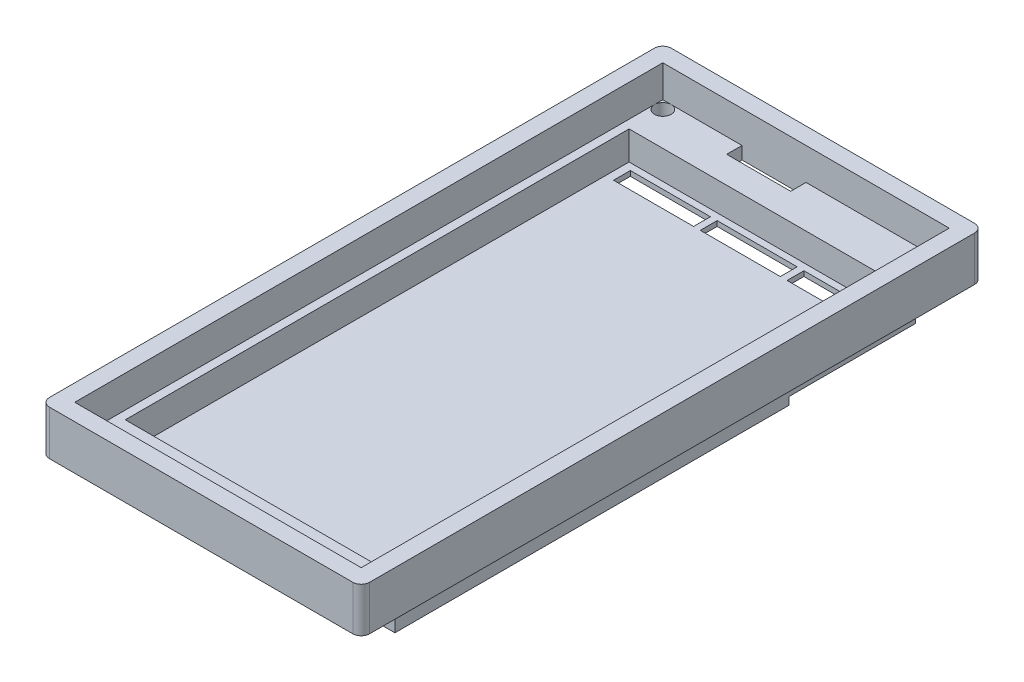
SolidWorks part; units mm, degrees
ref_plane "Front Plane" through (0, 0, 0) normal (0, 0, 1) x (1, 0, 0)
ref_plane "Top Plane" through (0, 0, 0) normal (0, 1, 0) x (1, 0, 0)
ref_plane "Right Plane" through (0, 0, 0) normal (1, 0, 0) x (0, 0, -1)
ref_axis "X-Axis" through (-88.99, 0, 0) along (1, 0, 0)
ref_axis "Y-Axis" through (0, 55, 0) along (0, -1, 0)
ref_axis "Z-Axis" through (0, 0, -88.99) along (0, 0, 1)
sketch "Sketch1" plane through (0, 0, 0) normal (0, 1, 0) x (1, 0, 0)
  line L1 (-19, -36.9) -> (19, -36.9)
  line L2 (-19, -36.9) -> (-19, 36.9)
  line L3 (-19, 36.9) -> (19, 36.9)
  line L4 (19, -36.9) -> (19, 36.9)
  line L5 (-19, -36.9) -> (19, 36.9) construction
  line L6 (-19, 36.9) -> (19, -36.9) construction
  point P0 (0, 0)
  dimension "D1" = 73.8
  dimension "D2" = 38
extrude "Boss-Extrude1" add sketch "Sketch1" along normal blind 1.5
sketch "Sketch2" plane through (0, 1.5, 0) normal (0, 1, 0) x (1, 0, 0)
  line L8 (17, -34.9) -> (17, 34.9)
  line L9 (17, 34.9) -> (-17, 34.9)
  line L10 (-17, 34.9) -> (-17, -34.9)
  line L11 (-17, -34.9) -> (17, -34.9)
  line L12 (17, -34.9) -> (17, 34.9)
  line L13 (17, 34.9) -> (-17, 34.9)
  line L14 (-17, 34.9) -> (-17, -34.9)
  line L15 (-17, -34.9) -> (17, -34.9)
  line L20 (19, -36.9) -> (19, 36.9)
  line L21 (19, 36.9) -> (-19, 36.9)
  line L22 (-19, 36.9) -> (-19, -36.9)
  line L23 (-19, -36.9) -> (19, -36.9)
  line L24 (19, -36.9) -> (19, 36.9)
  line L25 (19, 36.9) -> (-19, 36.9)
  line L26 (-19, 36.9) -> (-19, -36.9)
  line L27 (-19, -36.9) -> (19, -36.9)
  dimension "D1" = 2
  dimension "D2" = 0
extrude "Boss-Extrude2" add sketch "Sketch2" along normal blind 3.8
fillet "Fillet1" radius 1 4 edges at (19, 2.65, -36.9) (-19, 2.65, -36.9) (19, 2.65, 36.9) (-19, 2.65, 36.9)
sketch "Sketch3" plane through (0, 1.5, 0) normal (0, 1, 0) x (1, 0, 0)
  line L0 (-17, 33.9) -> (-16, 33.9) construction
  line L1 (-17, 34.9) -> (-17, -34.9) construction
  line L2 (-16, 33.9) -> (16, 33.9) construction
  line L3 (16, 33.9) -> (17, 33.9) construction
  line L4 (17, -34.9) -> (17, 34.9) construction
  line L5 (17, 34.9) -> (-17, 34.9) construction
  circle A0 centre (-16, 33.9) radius 1
  circle A1 centre (16, 33.9) radius 1
  dimension "D2" = 2
  dimension "D1" = 1
  dimension "D3" = 1
extrude "Cut-Extrude1" cut sketch "Sketch3" against normal through all
mirror "Mirror1" about plane through (0, 0, 0) normal (0, 0, 1) of "Cut-Extrude1"
sketch "Sketch4" plane through (0, 1.5, 0) normal (0, 1, 0) x (1, 0, 0)
  line L0 (17, 34.9) -> (-17, 34.9) construction
  line L1 (-7.6, 34.9) -> (0, 34.9)
  line L2 (-7.6, 34.9) -> (-7.6, 33.08)
  line L3 (-7.6, 33.08) -> (0, 33.08)
  line L4 (0, 34.9) -> (0, 33.08)
  line L5 (-17, 33.9) -> (-17, -33.9) construction
  dimension "D1" = 1.82
  dimension "D2" = 9.4
  dimension "D3" = 7.6
extrude "Cut-Extrude2" cut sketch "Sketch4" against normal through all
sketch "Sketch5" plane through (0, 1.5, 0) normal (0, 1, 0) x (1, 0, 0)
  line L0 (-17, 28.1) -> (-10.3, 28.1) construction
  line L1 (-10.3, 28.1) -> (10.3, 28.1) construction
  line L2 (10.3, 28.1) -> (17, 28.1) construction
  line L3 (-17, 34.9) -> (-17, -34.9) construction
  line L4 (17, -34.9) -> (17, 34.9) construction
  line L5 (0, 0) -> (0, 28.1) construction
  line L6 (17, 34.9) -> (-17, 34.9) construction
  line L7 (-15.05, 29.1) -> (-5.55, 29.1)
  line L8 (-15.05, 29.1) -> (-15.05, 27.1)
  line L9 (-15.05, 27.1) -> (-5.55, 27.1)
  line L10 (-5.55, 29.1) -> (-5.55, 27.1)
  line L11 (-15.05, 29.1) -> (-5.55, 27.1) construction
  line L12 (-15.05, 27.1) -> (-5.55, 29.1) construction
  line L13 (-4.75, 29.1) -> (4.75, 29.1)
  line L14 (-4.75, 29.1) -> (-4.75, 27.1)
  line L15 (-4.75, 27.1) -> (4.75, 27.1)
  line L16 (4.75, 29.1) -> (4.75, 27.1)
  line L17 (-4.75, 29.1) -> (4.75, 27.1) construction
  line L18 (-4.75, 27.1) -> (4.75, 29.1) construction
  line L19 (5.55, 29.1) -> (15.05, 29.1)
  line L20 (5.55, 29.1) -> (5.55, 27.1)
  line L21 (5.55, 27.1) -> (15.05, 27.1)
  line L22 (15.05, 29.1) -> (15.05, 27.1)
  line L23 (5.55, 29.1) -> (15.05, 27.1) construction
  line L24 (5.55, 27.1) -> (15.05, 29.1) construction
  dimension "D1" = 6.7
  dimension "D2" = 9.5
  dimension "D3" = 2
  dimension "D4" = 6.8
  dimension "D5" = 6.8
extrude "Cut-Extrude3" cut sketch "Sketch5" against normal through all
pattern_linear "LPattern1" count 2 spacing 56 along (0, 0, 1) of "Cut-Extrude3"
sketch "Sketch6" plane through (0, 0, 0) normal (0, -1, 0) x (1, 0, 0)
  line L0 (-18, 36.9) -> (18, 36.9) construction
  line L1 (-17, -30.9) -> (17, -30.9)
  line L2 (-17, -30.9) -> (-17, 30.9)
  line L3 (-17, 30.9) -> (17, 30.9)
  line L4 (17, -30.9) -> (17, 30.9)
  line L5 (18, -36.9) -> (-18, -36.9) construction
  line L6 (19, 35.9) -> (19, -35.9) construction
  line L7 (-19, -35.9) -> (-19, 35.9) construction
  line L73 (-5.55, 26.9) -> (-5.55, 28.9)
  line L74 (-15.05, 26.9) -> (-5.55, 26.9)
  line L75 (-15.05, 28.9) -> (-15.05, 26.9)
  line L76 (-5.55, 28.9) -> (-15.05, 28.9)
  line L77 (-5.55, 26.9) -> (-5.55, 28.9)
  line L78 (-15.05, 26.9) -> (-5.55, 26.9)
  line L79 (-15.05, 28.9) -> (-15.05, 26.9)
  line L80 (-5.55, 28.9) -> (-15.05, 28.9)
  line L87 (4.75, 26.9) -> (4.75, 28.9)
  line L88 (4.75, 28.9) -> (-4.75, 28.9)
  line L89 (-4.75, 26.9) -> (4.75, 26.9)
  line L90 (-4.75, 28.9) -> (-4.75, 26.9)
  line L91 (4.75, 26.9) -> (4.75, 28.9)
  line L92 (4.75, 28.9) -> (-4.75, 28.9)
  line L93 (-4.75, 26.9) -> (4.75, 26.9)
  line L94 (-4.75, 28.9) -> (-4.75, 26.9)
  line L99 (5.55, 26.9) -> (15.05, 26.9)
  line L100 (15.05, 26.9) -> (15.05, 28.9)
  line L101 (15.05, 28.9) -> (5.55, 28.9)
  line L102 (5.55, 28.9) -> (5.55, 26.9)
  line L103 (5.55, 26.9) -> (15.05, 26.9)
  line L104 (15.05, 26.9) -> (15.05, 28.9)
  line L105 (15.05, 28.9) -> (5.55, 28.9)
  line L106 (5.55, 28.9) -> (5.55, 26.9)
  line L111 (-15.05, -29.1) -> (-5.55, -29.1)
  line L112 (-5.55, -29.1) -> (-5.55, -27.1)
  line L113 (-5.55, -27.1) -> (-15.05, -27.1)
  line L114 (-15.05, -27.1) -> (-15.05, -29.1)
  line L115 (-15.05, -29.1) -> (-5.55, -29.1)
  line L116 (-5.55, -29.1) -> (-5.55, -27.1)
  line L117 (-5.55, -27.1) -> (-15.05, -27.1)
  line L118 (-15.05, -27.1) -> (-15.05, -29.1)
  line L123 (-4.75, -29.1) -> (4.75, -29.1)
  line L124 (4.75, -29.1) -> (4.75, -27.1)
  line L125 (4.75, -27.1) -> (-4.75, -27.1)
  line L126 (-4.75, -27.1) -> (-4.75, -29.1)
  line L127 (-4.75, -29.1) -> (4.75, -29.1)
  line L128 (4.75, -29.1) -> (4.75, -27.1)
  line L129 (4.75, -27.1) -> (-4.75, -27.1)
  line L130 (-4.75, -27.1) -> (-4.75, -29.1)
  line L135 (15.05, -29.1) -> (15.05, -27.1)
  line L136 (5.55, -29.1) -> (15.05, -29.1)
  line L137 (5.55, -27.1) -> (5.55, -29.1)
  line L138 (15.05, -27.1) -> (5.55, -27.1)
  line L139 (15.05, -29.1) -> (15.05, -27.1)
  line L140 (5.55, -29.1) -> (15.05, -29.1)
  line L141 (5.55, -27.1) -> (5.55, -29.1)
  line L142 (15.05, -27.1) -> (5.55, -27.1)
  dimension "D1" = 6
  dimension "D2" = 6
  dimension "D3" = 2
  dimension "D4" = 2
  dimension "D5" = 0
  dimension "D6" = 0
  dimension "D7" = 0
  dimension "D8" = 0
  dimension "D9" = 0
  dimension "D10" = 0
extrude "Boss-Extrude3" add sketch "Sketch6" along normal blind 3.4
sketch "Sketch7" plane through (0, 1.5, 0) normal (0, 1, 0) x (1, 0, 0)
  line L11 (-16, -29.9) -> (16, -29.9)
  line L12 (-16, 29.9) -> (-16, -29.9)
  line L13 (16, -29.9) -> (16, 29.9)
  line L14 (16, 29.9) -> (-16, 29.9)
  line L15 (-16, -29.9) -> (16, -29.9)
  line L16 (-16, 29.9) -> (-16, -29.9)
  line L17 (16, -29.9) -> (16, 29.9)
  line L18 (16, 29.9) -> (-16, 29.9)
  dimension "D1" = 1
extrude "Cut-Extrude5" cut sketch "Sketch7" against normal blind 3.4
sketch "Sketch9" plane through (17, 0, 0) normal (1, 0, 0) x (0, 0, -1)
  line L1 (30.9, -3.4) -> (15.9, -3.4)
  line L2 (30.9, -3.4) -> (30.9, -2.5)
  line L3 (30.9, -2.5) -> (15.9, -2.5)
  line L4 (15.9, -3.4) -> (15.9, -2.5)
  dimension "D1" = 15
  dimension "D2" = 0.9
extrude "Cut-Extrude7" cut sketch "Sketch9" against normal through all
sketch "Sketch10" plane through (-17, 0, 0) normal (-1, 0, 0) x (0, 0, 1)
  line L0 (30.9, -3.4) -> (-15.9, -3.4) construction
  line L1 (-9.1, -3.4) -> (0.9, -3.4)
  line L2 (-9.1, -3.4) -> (-9.1, -2.9)
  line L3 (-9.1, -2.9) -> (0.9, -2.9)
  line L4 (0.9, -3.4) -> (0.9, -2.9)
  line L5 (30.9, -3.4) -> (30.9, 0) construction
  dimension "D1" = 10
  dimension "D2" = 0.5
  dimension "D3" = 30
extrude "Cut-Extrude8" cut sketch "Sketch10" against normal blind 7
